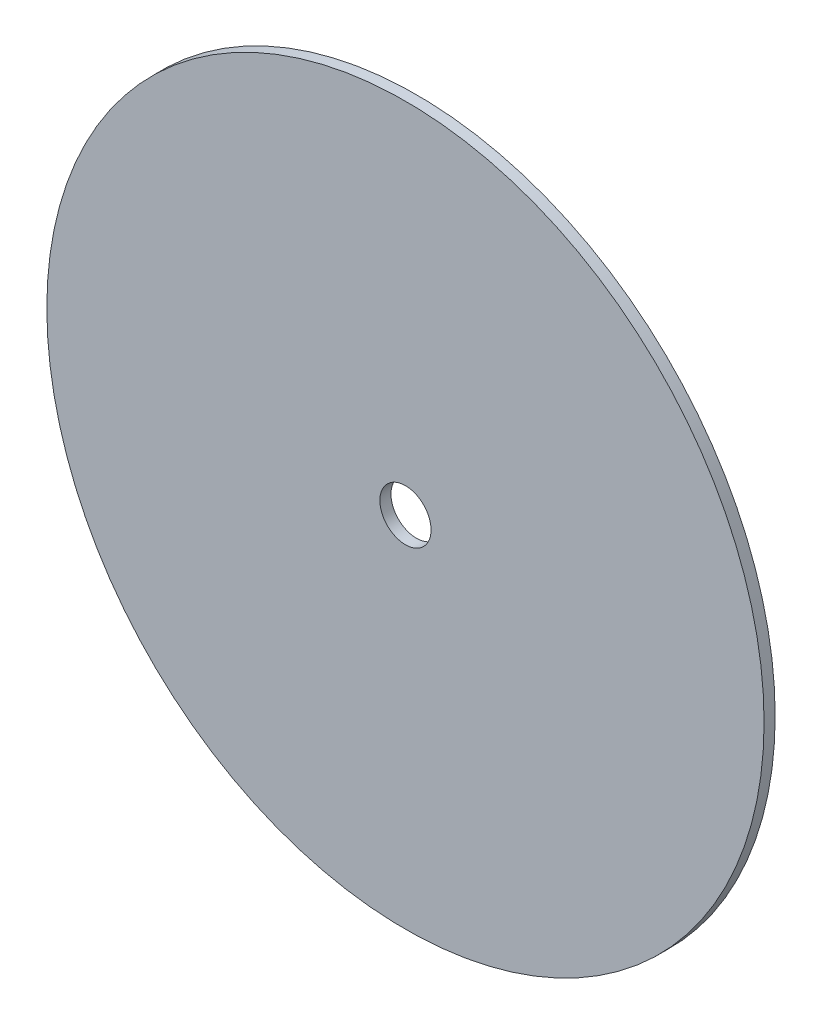
SolidWorks part; units mm, degrees
ref_plane "Front Plane" through (0, 0, 0) normal (0, 0, 1) x (1, 0, 0)
ref_plane "Top Plane" through (0, 0, 0) normal (0, 1, 0) x (1, 0, 0)
ref_plane "Right Plane" through (0, 0, 0) normal (1, 0, 0) x (0, 0, -1)
sketch "Sketch1" plane through (0, 0, 0) normal (0, 0, 1) x (1, 0, 0)
  circle A0 centre (0, 0) radius 20.1549
  circle A1 centre (0, 0) radius 0.4984
sketch "Sketch11" plane through (0, 0, 0) normal (0, 0, 1) x (1, 0, 0)
  circle A0 centre (0, 0) radius 23.8196
  circle A1 centre (0, 0) radius 1.6992
base flange "Base-Flange2" sketch "Sketch11" thickness 0.7366 reverse thickness direction no parameters "D1"=0.7366
sketch "Bend-Lines1" plane through (0, 0, 0) normal (0, 1, 0) x (1, 0, 0)
sketch "Bounding-Box1" plane through (0, 0, 0) normal (0, 1, 0) x (1, 0, 0)
sheet metal parameters "Sheet-Metal7" thickness 0.7366 parameters "D1"=0.7366
flat pattern "Flat-Pattern7" [suppressed]
sketch "Bend-Lines3" plane through (0, 0, 0) normal (0, 1, 0) x (1, 0, 0)
sketch "Bounding-Box3" [suppressed] plane through (0, 0, 0) normal (0, 1, 0) x (1, 0, 0)
